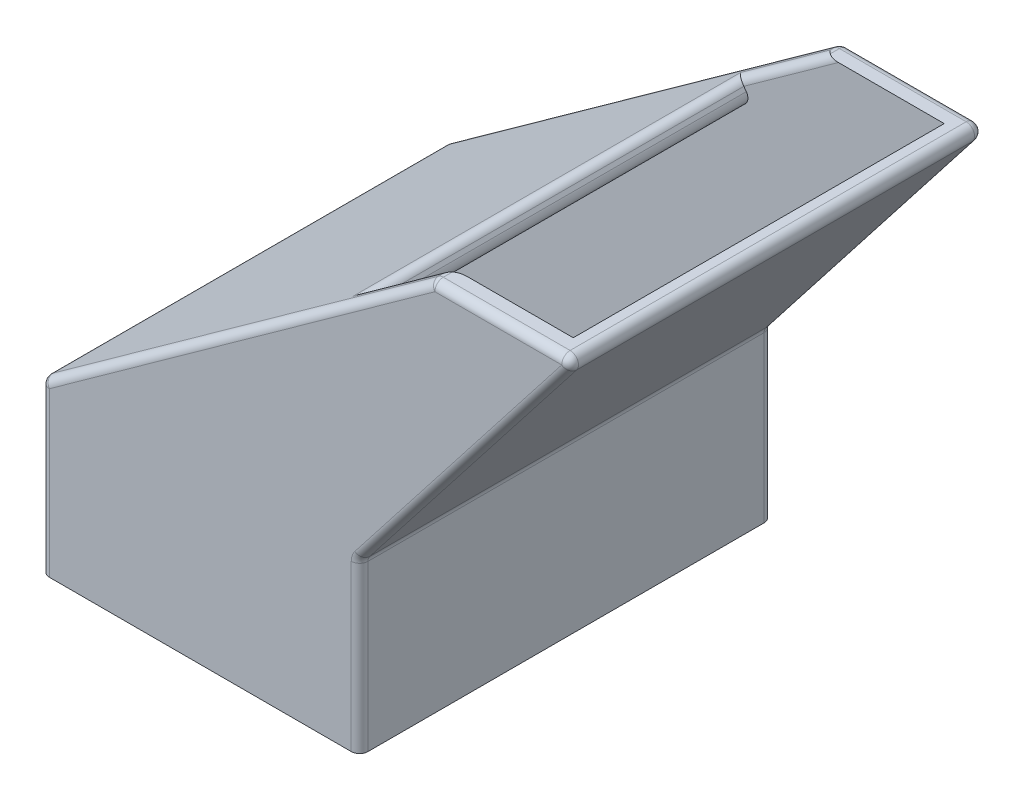
SolidWorks part; units mm, degrees
ref_plane "Front" through (0, 0, 0) normal (0, 0, 1) x (1, 0, 0)
ref_plane "Top" through (0, 0, 0) normal (0, 1, 0) x (1, 0, 0)
ref_plane "Right" through (0, 0, 0) normal (1, 0, 0) x (0, 0, -1)
sketch "Sketch1" plane through (0, 0, 0) normal (0, 1, 0) x (1, 0, 0)
  line L1 (-7.6, 9.85) -> (7.6, 9.85)
  line L2 (-7.6, 9.85) -> (-7.6, -9.85)
  line L3 (-7.6, -9.85) -> (7.6, -9.85)
  line L4 (7.6, 9.85) -> (7.6, -9.85)
  point P4 (0, 9.85)
  point P6 (-7.6, 0)
  dimension "D1" = 15.2
  dimension "D2" = 19.7
extrude "Extrude1" add sketch "Sketch1" along normal blind 8
sketch "Sketch12" plane through (0, 0, 0) normal (0, 0, 1) x (1, 0, 0)
  line L0 (0, 0) -> (-6.5, 11.2583) construction
  line L1 (-6.5, 11.2583) -> (13.1111, 22.5808) construction
  line L3 (-7.6, 0) -> (7.6, 0) construction
  dimension "D1" = 13
  dimension "D2" = 60
sketch "Sketch11" plane through (0, 0, 9.85) normal (0, 0, 1) x (1, 0, 0)
  line L0 (-7.6, 8) -> (11.0633, 21.3985)
  line L1 (11.0633, 21.3985) -> (18.0633, 21.3985)
  line L2 (18.0633, 21.3985) -> (7.6, 8)
  line L3 (7.6, 8) -> (-7.6, 8)
  line L4 (-6.5, 11.2583) -> (13.1111, 22.5808) construction
  dimension "D1" = 7
  dimension "D2" = 17
extrude "Boss-Extrude1" add sketch "Sketch11" against normal up to surface (19.7 mm away) up to face at (0, 4, -9.85)
shell "Shell1" thickness 1 removed face at (0, 0, 0) removed face at (14.5633, 21.3985, 0)
sketch "Sketch5" plane through (0, 0, 0) normal (0, -1, 0) x (1, 0, 0)
  line L0 (-7.6, -9.85) -> (-7.6, 9.85) construction
  circle A0 centre (-7.6, 0) radius 0.5
  dimension "D1" = 1
extrude "Extrude4" add sketch "Sketch5" against normal blind 5
sketch "Sketch9" plane through (0, 0, 0) normal (0, 0, 1) x (1, 0, 0)
  line L0 (-7.6, 0) -> (-8.1, 1.2)
  line L1 (-8.1, 5) -> (-8.1, 0) construction
  line L2 (-7.6, 0) -> (-8.1, 0)
  line L3 (-8.1, 0) -> (-8.1, 1.2)
  dimension "D1" = 1.2
extrude "Extrude7" cut sketch "Sketch9" against normal through all both and the other way through all
ref_plane "Plane1" through (17.438, 12.5189, 0) normal (0.8123, 0.5832, 0) x (0, 0, 1)
sketch "Sketch14" plane through (17.438, 12.5189, 0) normal (0.8123, 0.5832, 0) x (0, 0, 1)
  line L0 (-9.85, -10.9309) -> (9.85, -10.9309) construction
  line L1 (-8.85, -9.9309) -> (8.85, -9.9309)
  line L2 (-8.85, -9.9309) -> (-8.85, -10.9309)
  line L3 (-8.85, -10.9309) -> (8.85, -10.9309)
  line L4 (8.85, -9.9309) -> (8.85, -10.9309)
extrude "Cut-Extrude1" cut sketch "Sketch14" along normal through all and the other way blind 5
fillet "Fillet1" radius 0.4 18 edges at (7.0016, 18.4826, 0) (9.0324, 19.9405, 8.85) (11.0633, 21.3985, 9.35) (-7.6, 8, 0) (11.0633, 21.3985, -9.35) (9.0324, 19.9405, -8.85) (18.0633, 21.3985, 0) (7.6, 8, 0) (-7.6, 4, 9.85) (1.7316, 14.6992, 9.85) (14.5633, 21.3985, 9.85) (12.8316, 14.6992, 9.85) (7.6, 4, 9.85) (7.6, 4, -9.85) (12.8316, 14.6992, -9.85) (14.5633, 21.3985, -9.85) (1.7316, 14.6992, -9.85) (-7.6, 4, -9.85)
fillet "Fillet3" radius 0.4 1 edges at (7.5848, 17.6702, 0)
fillet "Fillet4" radius 5 2 edges at (-6.6, 7.4869, 0) (6.6, 8.3442, 0)
